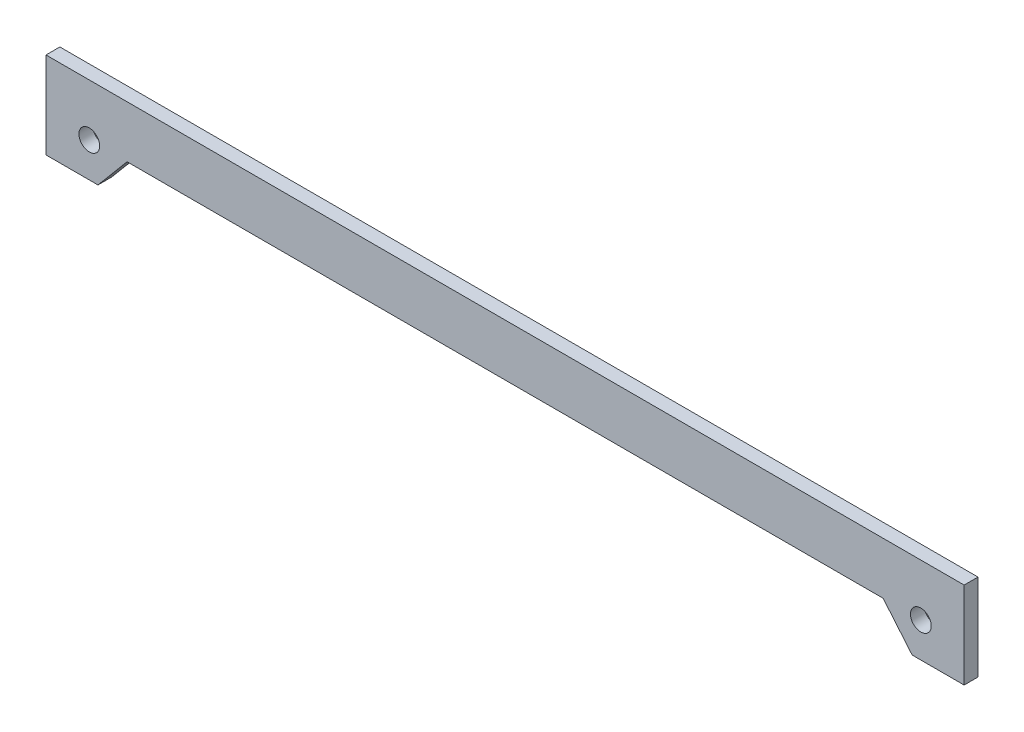
SolidWorks part; units mm, degrees
material "Pappelsperrholz"
ref_plane "Ebene vorne" through (0, 0, 0) normal (0, 0, 1) x (1, 0, 0)
ref_plane "Ebene oben" through (0, 0, 0) normal (0, 1, 0) x (1, 0, 0)
ref_plane "Ebene rechts" through (0, 0, 0) normal (1, 0, 0) x (0, 0, -1)
sketch "Skizze1" plane through (0, 0, 0) normal (0, 0, 1) x (1, 0, 0)
  line L0 (0, 0) -> (0, -22.0536) construction
  line L1 (132.5, 0) -> (-132.5, 0)
  line L2 (-132.5, 0) -> (-132.5, -25)
  line L3 (-132.5, -25) -> (-117.5, -25)
  line L4 (-117.5, -25) -> (-109.109, -15)
  line L5 (-109.109, -15) -> (109.109, -15)
  line L6 (117.5, -25) -> (109.109, -15)
  line L7 (132.5, -25) -> (117.5, -25)
  line L8 (132.5, 0) -> (132.5, -25)
  point P9 (0, -15)
  dimension "D1" = 265
  dimension "D2" = 25
  dimension "D3" = 15
  dimension "D4" = 15
  dimension "D5" = 130
extrude "Grundplatte" add sketch "Skizze1" along normal blind 4
sketch "Skizze2" plane through (0, 0, 4) normal (0, 0, 1) x (1, 0, 0)
  line L0 (0, 0) -> (0, -15) construction
  line L1 (-109.109, -15) -> (109.109, -15) construction
  line L2 (132.5, 0) -> (-132.5, 0) construction
  circle A0 centre (-120, -15) radius 3
  circle A1 centre (120, -15) radius 3
  dimension "D1" = 6
  dimension "D3" = 240
  dimension "D2" = 15
extrude "Schnitt-Linear austragen1" cut sketch "Skizze2" against normal through all
